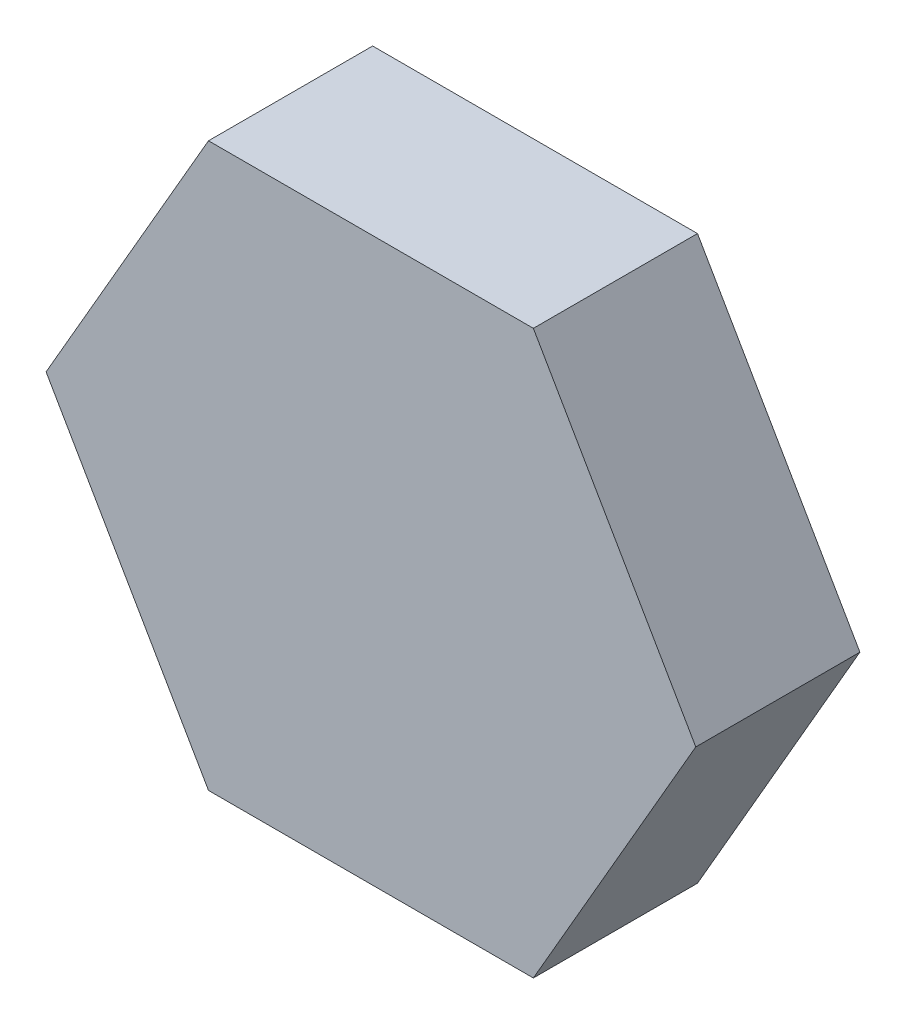
SolidWorks part; units mm, degrees
ref_plane "Plan de face" through (0, 0, 0) normal (0, 0, 1) x (1, 0, 0)
ref_plane "Plan de dessus" through (0, 0, 0) normal (0, 1, 0) x (1, 0, 0)
ref_plane "Plan de droite" through (0, 0, 0) normal (1, 0, 0) x (0, 0, -1)
sketch "Esquisse2" plane through (0, 0, 0) normal (0, 0, 1) x (1, 0, 0)
  line L1 (47.5, 0) -> (23.75, 41.1362)
  line L2 (23.75, 41.1362) -> (-23.75, 41.1362)
  line L3 (-23.75, 41.1362) -> (-47.5, 0)
  line L4 (-47.5, 0) -> (-23.75, -41.1362)
  line L5 (-23.75, -41.1362) -> (23.75, -41.1362)
  line L6 (23.75, -41.1362) -> (47.5, 0)
  circle A0 centre (0, 0) radius 41.1362 construction
  dimension "D1" = 95
extrude "Boss.-Extru.1" add sketch "Esquisse2" along normal blind 24
